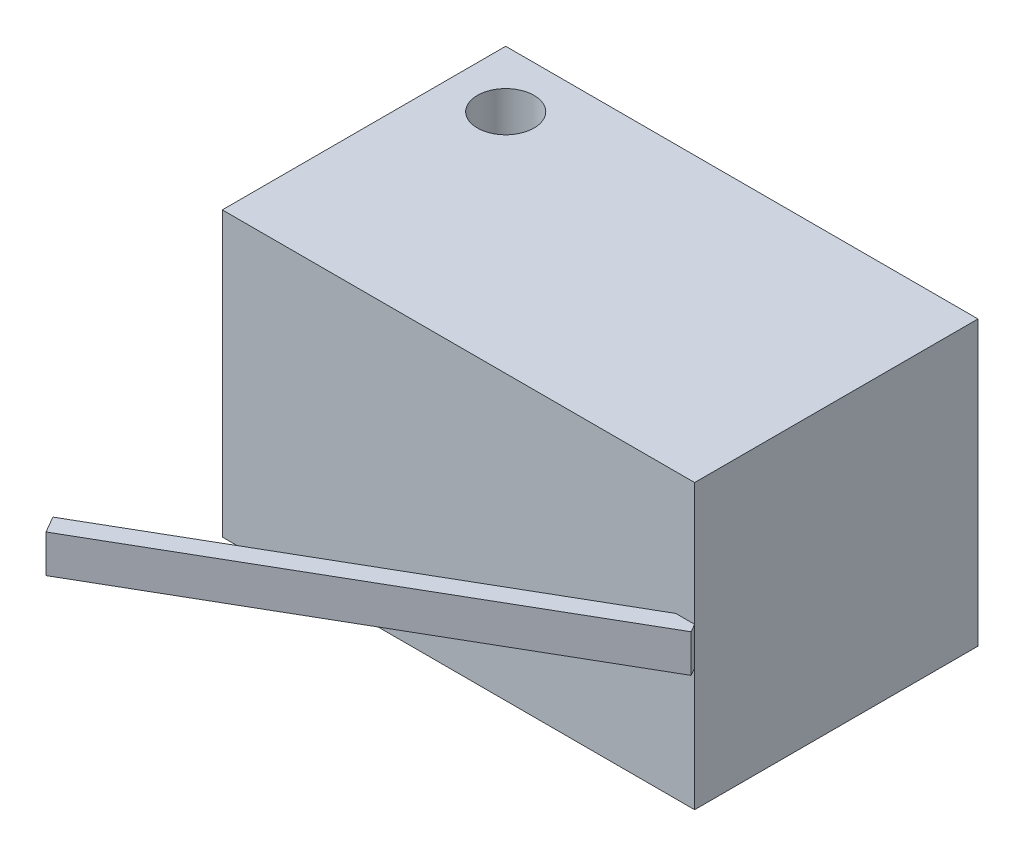
SolidWorks part; units mm, degrees
ref_plane "Front Plane" through (0, 0, 0) normal (0, 0, 1) x (1, 0, 0)
ref_plane "Top Plane" through (0, 0, 0) normal (0, 1, 0) x (1, 0, 0)
ref_plane "Right Plane" through (0, 0, 0) normal (1, 0, 0) x (0, 0, -1)
sketch "Sketch1" plane through (0, 0, 0) normal (0, 1, 0) x (1, 0, 0)
  line L1 (12.5, -7.5) -> (-12.5, -7.5)
  line L2 (12.5, -7.5) -> (12.5, 7.5)
  line L3 (12.5, 7.5) -> (-12.5, 7.5)
  line L4 (-12.5, -7.5) -> (-12.5, 7.5)
  line L5 (12.5, -7.5) -> (-12.5, 7.5) construction
  line L6 (12.5, 7.5) -> (-12.5, -7.5) construction
  point P0 (0, 0)
  dimension "D1" = 15
  dimension "D2" = 25
extrude "Boss-Extrude1" add sketch "Sketch1" along normal blind 15
ref_plane "Plane1" through (6.3726, 0, 11.0377) normal (0.5, 0, 0.866) x (0, -1, 0)
sketch "Sketch2" plane through (6.3726, 0, 11.0377) normal (0.5, 0, 0.866) x (0, -1, 0)
  line L0 (-15, 7.0753) -> (0, 7.0753) construction
  line L1 (-8.5, -17.9247) -> (-6.5, -17.9247)
  line L2 (-8.5, -17.9247) -> (-8.5, 7.0753)
  line L3 (-8.5, 7.0753) -> (-6.5, 7.0753)
  line L4 (-6.5, -17.9247) -> (-6.5, 7.0753)
  point P6 (-7.5, 7.0753)
  point P7 (-7.5, 7.0753)
  point P10 (-3.8123, -14.1421)
  dimension "D1" = 25
  dimension "D2" = 2
extrude "Boss-Extrude2" add sketch "Sketch2" along normal mid plane 1
sketch "Sketch3" plane through (0, 15, 0) normal (0, 1, 0) x (1, 0, 0)
  line L0 (-12.5, 7.5) -> (-12.5, -7.5) construction
  line L2 (12.5, 7.5) -> (-12.5, 7.5) construction
  circle A0 centre (-9.5, 4.5) radius 1.5
  point P4 (0, 0)
  point P6 (-9.3004, -5.6741)
  dimension "D1" = 3
  dimension "D2" = 3
  dimension "D3" = 3
extrude "Cut-Extrude1" cut sketch "Sketch3" against normal up to surface (15 mm away) up to face at (0, 0, 0)
